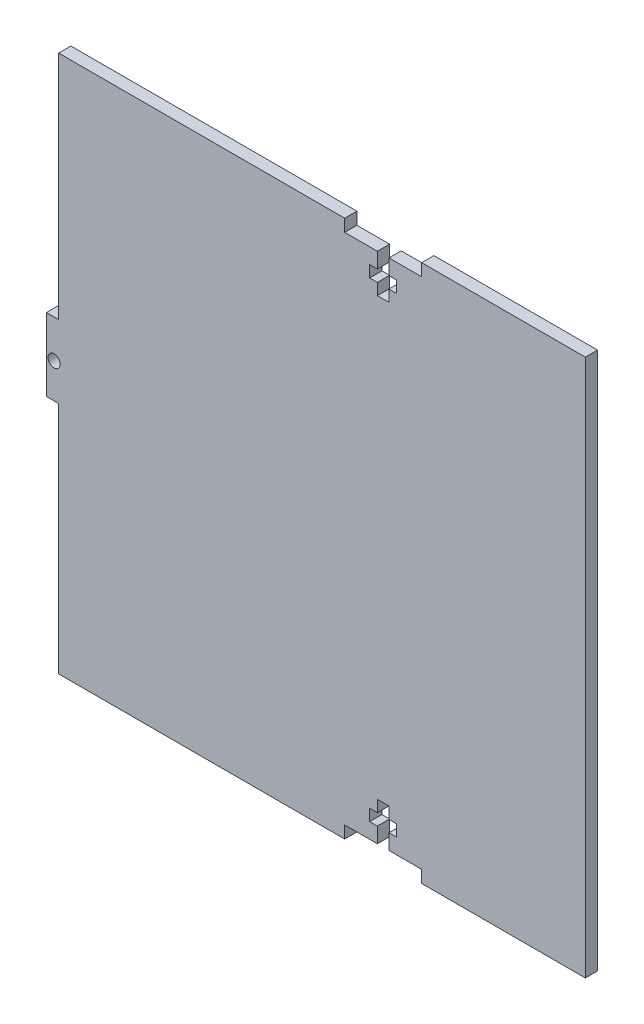
SolidWorks part; units mm, degrees
ref_plane "Front Plane" through (0, 0, 0) normal (0, 0, 1) x (1, 0, 0)
ref_plane "Top Plane" through (0, 0, 0) normal (0, 1, 0) x (1, 0, 0)
ref_plane "Right Plane" through (0, 0, 0) normal (1, 0, 0) x (0, 0, -1)
sketch "Sketch1" plane through (0, 0, 0) normal (0, 0, 1) x (1, 0, 0)
  line L1 (-87.5, 69.85) -> (87.5, 69.85)
  line L2 (-87.5, 69.85) -> (-87.5, -69.85)
  line L3 (-87.5, -69.85) -> (87.5, -69.85)
  line L4 (87.5, 69.85) -> (87.5, -69.85)
  line L5 (-87.5, 69.85) -> (87.5, -69.85) construction
  line L6 (-87.5, -69.85) -> (87.5, 69.85) construction
  point P0 (0, 0)
  dimension "D1" = 139.7
  dimension "D2" = 175
extrude "Boss-Extrude1" add sketch "Sketch1" along normal blind 3.18
sketch "Sketch2" plane through (0, 0, 3.18) normal (0, 0, 1) x (1, 0, 0)
  line L0 (0, 0) -> (87.5, 0) construction
  line L1 (-10, 69.85) -> (10, 69.85)
  line L2 (-10, 69.85) -> (-10, 66.67)
  line L3 (-10, 66.67) -> (-1.5, 66.67)
  line L4 (10, 69.85) -> (10, 66.67)
  line L5 (87.5, -69.85) -> (87.5, 69.85) construction
  line L6 (0, 0) -> (0, 69.85) construction
  line L7 (-1.5, 56.67) -> (1.5, 56.67)
  line L8 (-1.5, 56.67) -> (-1.5, 59.67)
  line L10 (1.5, 56.67) -> (1.5, 59.67)
  line L12 (87.5, 69.85) -> (-87.5, 69.85) construction
  line L13 (3.5, 62.67) -> (1.5, 62.67)
  line L14 (3.5, 62.67) -> (3.5, 59.67)
  line L15 (3.5, 59.67) -> (1.5, 59.67)
  line L16 (-3.5, 62.67) -> (-3.5, 59.67)
  line L17 (-10, -69.85) -> (-10, -66.67)
  line L18 (-10, -66.67) -> (-1.5, -66.67)
  line L19 (-1.5, -62.67) -> (-1.5, -66.67)
  line L20 (-1.5, -62.67) -> (-3.5, -62.67)
  line L21 (-3.5, -62.67) -> (-3.5, -59.67)
  line L22 (1.5, 66.67) -> (10, 66.67)
  line L23 (-1.5, 62.67) -> (-3.5, 62.67)
  line L24 (-1.5, -59.67) -> (-3.5, -59.67)
  line L25 (-1.5, -56.67) -> (-1.5, -59.67)
  line L26 (-1.5, -56.67) -> (1.5, -56.67)
  line L27 (-1.5, 59.67) -> (-3.5, 59.67)
  line L28 (1.5, -56.67) -> (1.5, -59.67)
  line L29 (-1.5, 62.67) -> (-1.5, 66.67)
  line L30 (1.5, 62.67) -> (1.5, 66.67)
  line L31 (3.5, -59.67) -> (1.5, -59.67)
  line L32 (3.5, -62.67) -> (3.5, -59.67)
  line L33 (3.5, -62.67) -> (1.5, -62.67)
  line L34 (1.5, -62.67) -> (1.5, -66.67)
  line L35 (1.5, -66.67) -> (10, -66.67)
  line L36 (10, -69.85) -> (10, -66.67)
  line L37 (-10, -69.85) -> (10, -69.85)
  line L38 (-87.5, 69.85) -> (-87.5, -69.85) construction
  line L39 (-87.5, 69.85) -> (-84.32, 69.85)
  line L40 (-87.5, 69.85) -> (-87.5, 9.875)
  line L41 (-87.5, 9.875) -> (-84.32, 9.875)
  line L42 (-84.32, 69.85) -> (-84.32, 9.875)
  line L43 (-87.5, -69.85) -> (-84.32, -69.85)
  line L44 (-87.5, -69.85) -> (-87.5, -9.875)
  line L45 (-87.5, -9.875) -> (-84.32, -9.875)
  line L46 (-84.32, -69.85) -> (-84.32, -9.875)
  line L47 (87.5, -9.875) -> (84.32, -9.875)
  line L48 (84.32, -69.85) -> (84.32, -9.875)
  line L49 (87.5, -69.85) -> (84.32, -69.85)
  line L50 (87.5, -69.85) -> (87.5, -9.875)
  line L51 (87.5, 9.875) -> (84.32, 9.875)
  line L52 (84.32, 69.85) -> (84.32, 9.875)
  line L53 (87.5, 69.85) -> (84.32, 69.85)
  line L54 (87.5, 69.85) -> (87.5, 9.875)
  line L81 (0, 0) -> (0, -69.85) construction
  circle A0 centre (-85.5, 0) radius 1.5
  circle A1 centre (85.5, 0) radius 1.5
  point P0 (0, 50.5662)
  point P5 (0, 32.0079)
  point P10 (15.4931, 34.4893)
  dimension "D11" = 3
  dimension "D12" = 2
  dimension "D1" = 20
  dimension "D2" = 19.75
  dimension "D3" = 4
  dimension "D4" = 3
  dimension "D5" = 3.18
  dimension "D6" = 7
  dimension "D7" = 3
  dimension "D8" = 3
  dimension "D9" = 3.18
  dimension "D10" = 3.18
sketch "Sketch3" plane through (0, 0, 0) normal (0, 0, -1) x (-1, 0, 0)
  circle A0 centre (-35.6713, -47.9634) radius 1.59
  circle A1 centre (-35.6713, -30.7773) radius 1.59
extrude "Cut-Extrude2" cut sketch "Sketch3" against normal through all
sketch "Sketch4" plane through (0, 0, 0) normal (0, 0, -1) x (-1, 0, 0)
  circle A0 centre (-34.7507, 53.7803) radius 1.59
  circle A1 centre (-34.7507, 36.5942) radius 1.59
  circle A2 centre (36.2498, 53.7803) radius 1.59
  circle A3 centre (36.2498, 36.5942) radius 1.59
  circle A4 centre (35.9839, -30.7773) radius 1.59
  circle A5 centre (35.9839, -47.9634) radius 1.59
  circle A6 centre (-35.6713, -30.7773) radius 1.59
  circle A7 centre (-35.6713, -47.9634) radius 1.59
extrude "Cut-Extrude3" cut sketch "Sketch4" against normal through all
sketch "Sketch5" plane through (0, 0, 3.18) normal (0, 0, 1) x (1, 0, 0)
  line L1 (-46.5267, 67.382) -> (45.3995, 67.382)
  line L2 (-46.5267, 67.382) -> (-46.5267, -56.2746)
  line L3 (-46.5267, -56.2746) -> (45.3995, -56.2746)
  line L4 (45.3995, 67.382) -> (45.3995, -56.2746)
extrude "Boss-Extrude2" add sketch "Sketch5" against normal blind 3.18
sketch "Sketch6" plane through (0, 0, 0) normal (0, 0, -1) x (-1, 0, 0)
  line L1 (-26.8, -9.839) -> (-23.62, -9.839)
  line L2 (-26.8, -9.839) -> (-26.8, 9.911)
  line L3 (-26.8, 9.911) -> (-23.62, 9.911)
  line L4 (-23.62, -9.839) -> (-23.62, 9.911)
  line L5 (11.4836, -9.875) -> (14.6636, -9.875)
  line L6 (11.4836, -9.875) -> (11.4836, 9.875)
  line L7 (11.4836, 9.875) -> (14.6636, 9.875)
  line L8 (14.6636, -9.875) -> (14.6636, 9.875)
extrude "Cut-Extrude4" cut sketch "Sketch6" against normal through all
sketch "Sketch12" plane through (0, 0, 0) normal (0, 0, -1) x (-1, 0, 0)
  line L1 (40.471, -17.0656) -> (76.4831, -17.0656)
  line L2 (40.471, -17.0656) -> (40.471, 26.8946)
  line L3 (40.471, 26.8946) -> (76.4831, 26.8946)
  line L4 (76.4831, -17.0656) -> (76.4831, 26.8946)
  line L5 (40.471, -17.0656) -> (76.4831, 26.8946) construction
  line L6 (40.471, 26.8946) -> (76.4831, -17.0656) construction
  point P0 (58.477, 4.9145)
extrude "Cut-Extrude6" cut sketch "Sketch12" against normal through all
sketch "Sketch13" plane through (0, 0, 0) normal (0, 0, -1) x (-1, 0, 0)
  line L1 (-17.9359, -13.3526) -> (-1.7618, -13.3526)
  line L2 (-17.9359, -13.3526) -> (-17.9359, 13.3526)
  line L3 (-17.9359, 13.3526) -> (-1.7618, 13.3526)
  line L4 (-1.7618, -13.3526) -> (-1.7618, 13.3526)
  line L5 (-17.9359, -13.3526) -> (-1.7618, 13.3526) construction
  line L6 (-17.9359, 13.3526) -> (-1.7618, -13.3526) construction
  point P0 (-9.8488, 0)
extrude "Cut-Extrude7" cut sketch "Sketch13" against normal through all
sketch "Sketch14" plane through (0, 0, 0) normal (0, 0, -1) x (-1, 0, 0)
  line L1 (-36.4871, -30.6985) -> (80.5501, -30.6985)
  line L2 (-36.4871, -30.6985) -> (-36.4871, 37.5545)
  line L3 (-36.4871, 37.5545) -> (80.5501, 37.5545)
  line L4 (80.5501, -30.6985) -> (80.5501, 37.5545)
  line L5 (-36.4871, -30.6985) -> (80.5501, 37.5545) construction
  line L6 (-36.4871, 37.5545) -> (80.5501, -30.6985) construction
  point P0 (22.0315, 3.428)
extrude "Boss-Extrude5" add sketch "Sketch14" against normal blind 3.18
sketch "Sketch16" plane through (0, 0, 0) normal (0, 0, -1) x (-1, 0, 0)
  circle A0 centre (-83.6064, 0) radius 1.6831
  circle A1 centre (84.6409, 1.0577) radius 2.4936
extrude "Boss-Extrude7" add sketch "Sketch16" against normal blind 3.18
sketch "Sketch17" plane through (0, 0, 0) normal (0, 0, -1) x (-1, 0, 0)
  line L0 (87.5, 69.85) -> (87.5, -69.85) construction
  line L1 (87.5, 69.85) -> (84.32, 69.85)
  line L2 (87.5, 69.85) -> (87.5, 10.7247)
  line L3 (87.5, 10.7247) -> (84.32, 10.7247)
  line L4 (84.32, 69.85) -> (84.32, 10.7247)
  line L5 (87.5, -69.85) -> (84.32, -69.85)
  line L6 (87.5, -69.85) -> (87.5, -9.0253)
  line L7 (87.5, -9.0253) -> (84.32, -9.0253)
  line L8 (84.32, -69.85) -> (84.32, -9.0253)
  circle A0 centre (85.5, 0) radius 1.59
  dimension "D3" = 3.18
  dimension "D1" = 19.75
  dimension "D2" = 3.18
  dimension "D4" = 2
extrude "Cut-Extrude8" cut sketch "Sketch17" against normal blind 10
sketch "Sketch18" plane through (0, 0, 0) normal (0, 0, -1) x (-1, 0, 0)
  line L0 (84.32, -69.85) -> (-87.5, -69.85) construction
  line L1 (-87.5, 69.85) -> (-36.2856, 69.85)
  line L2 (-87.5, 69.85) -> (-87.5, -69.85)
  line L3 (-87.5, -69.85) -> (-36.2856, -69.85)
  line L4 (-36.2856, 69.85) -> (-36.2856, -69.85)
extrude "Cut-Extrude9" cut sketch "Sketch18" against normal through all
sketch "Sketch19" plane through (0, 0, 0) normal (0, 0, -1) x (-1, 0, 0)
  line L0 (84.32, -69.85) -> (-36.2856, -69.85) construction
  line L1 (-36.2856, 69.85) -> (-52.5336, 69.85)
  line L2 (-36.2856, 69.85) -> (-36.2856, -69.85)
  line L3 (-36.2856, -69.85) -> (-52.5336, -69.85)
  line L4 (-52.5336, 69.85) -> (-52.5336, -69.85)
extrude "Boss-Extrude8" add sketch "Sketch19" against normal through all
extrude "Cut-Extrude10" cut sketch "Sketch2" against normal blind 5
